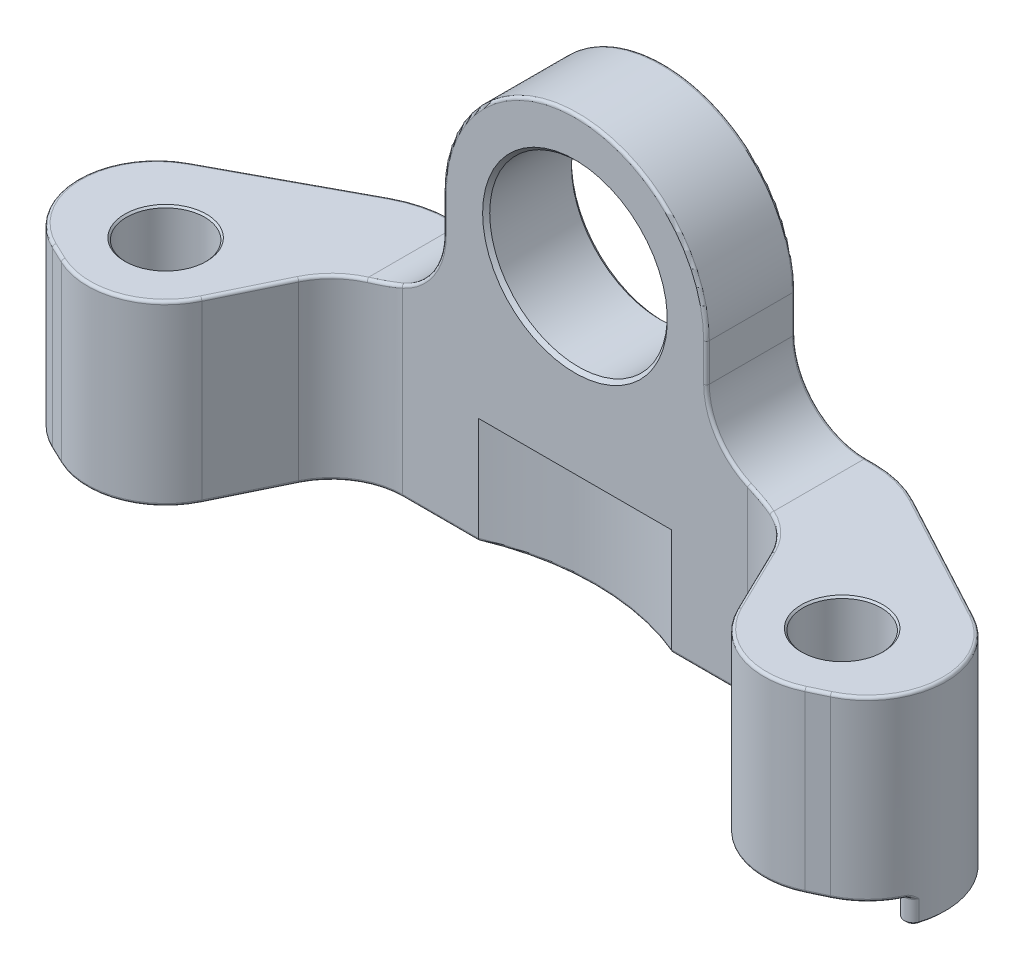
SolidWorks part; units mm, degrees
material "BOHLER M238"
ref_plane "Front Plane" through (0, 0, 0) normal (0, 0, 1) x (1, 0, 0)
ref_plane "Top Plane" through (0, 0, 0) normal (0, 1, 0) x (1, 0, 0)
ref_plane "Right Plane" through (0, 0, 0) normal (1, 0, 0) x (0, 0, -1)
sketch "Sketch1" plane through (0, 0, 0) normal (0, 1, 0) x (1, 0, 0)
  line L0 (0, 0) -> (0, 67.8527) construction
  line L1 (-59.4524, 45) -> (59.4524, 45)
  line L2 (0, 0) -> (0, -68.0986) construction
  line L3 (0, -44.3749) -> (-95.1623, 0) construction
  line L4 (0, -44.3749) -> (95.1623, 0) construction
  line L5 (73.649, 41.4283) -> (110.4109, 21.6808)
  line L6 (-73.649, 41.4283) -> (-110.4109, 21.6808)
  line L7 (109.4463, -17.5688) -> (104.6086, -19.8688)
  line L8 (66.4687, 8.7333) -> (75.3706, -9.6066)
  line L9 (48.4762, 20) -> (-48.4762, 20)
  line L10 (-66.4687, 8.7333) -> (-75.3706, -9.6066)
  line L11 (-109.4463, -17.5688) -> (-104.6086, -19.8688)
  arc A0 (109.4463, -17.5688) -> (110.4109, 21.6808) centre (100, 2.3) ccw
  arc A1 (-73.649, 41.4283) -> (-59.4524, 45) centre (-59.4524, 15) cw
  arc A2 (59.4524, 45) -> (73.649, 41.4283) centre (59.4524, 15) cw
  arc A3 (48.4762, 20) -> (66.4687, 8.7333) centre (48.4762, 0) cw
  arc A4 (-66.4687, 8.7333) -> (-48.4762, 20) centre (-48.4762, 0) cw
  arc A5 (-109.4463, -17.5688) -> (-110.4109, 21.6808) centre (-100, 2.3) cw
  circle A6 centre (-95.1623, 0) radius 11
  circle A7 centre (95.1623, 0) radius 11
  arc A8 (104.6086, -19.8688) -> (75.3706, -9.6066) centre (95.1623, 0) cw
  arc A9 (-75.3706, -9.6066) -> (-104.6086, -19.8688) centre (-95.1623, 0) cw
  circle A10 centre (0, -44.3749) radius 105 construction
  point P12 (0, 20)
  point P19 (0, 45)
  point P20 (-67, 45)
  point P23 (67, 45)
  point P26 (61, 20)
  point P29 (-61, 20)
  point P36 (84.8998, -29.239)
  point P39 (-84.8998, -29.239)
  dimension "D1" = 22
  dimension "D2" = 244
  dimension "D3" = 25
  dimension "D4" = 122
  dimension "D5" = 134
  dimension "D6" = 30
  dimension "D7" = 20
  dimension "D8" = 130
  dimension "D9" = 22
  dimension "D11" = 22
  dimension "D13" = 210
  dimension "D12" = 2.3
  dimension "D14" = 190.3246
  dimension "D10" = 20
extrude "Extrude1" add sketch "Sketch1" along normal blind 50
sketch "Sketch20" plane through (0, 0, -45) normal (0, 0, -1) x (-1, 0, 0)
  line L0 (-37, 80.6) -> (-37, 70)
  line L1 (37, 80.6) -> (37, 70)
  line L2 (-59.4524, 50) -> (59.4524, 50) construction
  line L3 (0, 80.6) -> (0, 15.3196) construction
  line L5 (57, 50) -> (0.0812, 50)
  line L6 (73.649, 50) -> (59.4524, 50) construction
  line L7 (-57, 50) -> (0.0812, 50)
  line L9 (-110.4109, 50) -> (-73.649, 50) construction
  line L10 (-110.4109, 0) -> (-73.649, 0) construction
  arc A0 (37, 80.6) -> (-37, 80.6) centre (0, 80.6) ccw
  circle A1 centre (0, 80.6) radius 24.9875
  arc A2 (37, 70) -> (57, 50) centre (57, 70) ccw
  arc A3 (-57, 50) -> (-37, 70) centre (-57, 70) ccw
  point P22 (37, 50)
  point P25 (-37, 50)
  dimension "D1" = 74
  dimension "D2" = 49.975
  dimension "D3" = 80.6
  dimension "D4" = 20
extrude "Boss-Extrude1" add sketch "Sketch20" against normal blind 40
sketch "Sketch21" plane through (0, 0, 0) normal (0, -1, 0) x (1, 0, 0)
  line L0 (-48.4762, -20) -> (48.4762, -20) construction
  line L1 (-48.4762, -20) -> (48.4762, -20)
  line L2 (-57, -18.0927) -> (-57, -5)
  line L3 (-57, -5) -> (57, -5)
  line L4 (57, -5) -> (-57, -5) construction
  line L5 (57, -5) -> (57, -18.0927)
  arc A0 (-57, -18.0927) -> (-48.4762, -20) centre (-48.4762, 0) ccw construction
  arc A1 (48.4762, -20) -> (57, -18.0927) centre (48.4762, 0) ccw construction
  arc A2 (-57, -18.0927) -> (-48.4762, -20) centre (-48.4762, 0) ccw
  arc A3 (48.4762, -20) -> (57, -18.0927) centre (48.4762, 0) ccw
extrude "Cut-Extrude6" cut sketch "Sketch21" against normal through all
chamfer "Chamfer6" distance 1 angle 45 2 edges at (-24.9875, 80.6, -45) (-24.9875, 80.6, -20)
sketch "Sketch24" plane through (0, 0, 0) normal (0, -1, 0) x (1, 0, 0)
  circle A0 centre (95.1623, 0) radius 14.515
  circle A1 centre (-95.1623, 0) radius 14.515
  dimension "D1" = 29.03
extrude "Cut-Extrude8" cut sketch "Sketch24" against normal blind 12
sketch "Sketch22" plane through (0, 0, 0) normal (0, -1, 0) x (1, 0, 0)
  line L0 (0, 0) -> (0, -36.5166) construction
  line L1 (-48.4762, -20) -> (48.4762, -20) construction
  line L2 (-27.1983, -20) -> (27.1983, -20)
  arc A0 (-27.1983, -20) -> (27.1983, -20) centre (0, 44.5) ccw
  dimension "D1" = 5.5
  dimension "D2" = 70
extrude "Cut-Extrude7" cut sketch "Sketch22" against normal blind 30
sketch "Sketch23" plane through (0, 0, 0) normal (0, -1, 0) x (1, 0, 0)
  line L0 (116.3612, 4.5259) -> (105.2255, -19.3547)
  line L1 (0, 0) -> (0, -63.7632) construction
  line L2 (-116.3612, 4.5259) -> (-105.2255, -19.3547)
  line L3 (-73.649, -41.4283) -> (-110.4109, -21.6808) construction
  line L4 (-108.6743, -22.6136) -> (-110.4109, -21.6808)
  line L5 (110.4109, -21.6808) -> (73.649, -41.4283) construction
  line L6 (110.4109, -21.6808) -> (108.6743, -22.6136)
  line L7 (59.4524, -45) -> (-59.4524, -45) construction
  line L9 (48.4762, -20) -> (27.1983, -20)
  line L10 (-27.1983, -20) -> (-48.4762, -20)
  line L11 (-66.4687, -8.7333) -> (-75.3706, 9.6066)
  line L12 (-104.6086, 19.8688) -> (-109.4463, 17.5688)
  line L13 (-110.4109, -21.6808) -> (-73.649, -41.4283)
  line L14 (-59.4524, -45) -> (59.4524, -45)
  line L15 (73.649, -41.4283) -> (110.4109, -21.6808)
  line L16 (109.4463, 17.5688) -> (104.6086, 19.8688)
  line L17 (75.3706, 9.6066) -> (66.4687, -8.7333)
  circle A1 centre (-95.1623, 0) radius 14.515 construction
  circle A2 centre (-95.1623, 0) radius 14.515 construction
  arc A3 (121.0151, 4.209) -> (116.3612, 4.5259) centre (118.627, 3.4694) ccw
  arc A4 (-116.3612, 4.5259) -> (-121.0151, 4.209) centre (-118.627, 3.4694) ccw
  arc A5 (105.2255, -19.3547) -> (108.6743, -22.6136) centre (107.4913, -20.4112) ccw
  arc A6 (-105.2255, -19.3547) -> (-108.6743, -22.6136) centre (-107.4913, -20.4112) cw
  arc A9 (-27.1983, -20) -> (27.1983, -20) centre (0, 44.5) ccw
  arc A10 (-66.4687, -8.7333) -> (-48.4762, -20) centre (-48.4762, 0) ccw
  arc A11 (-75.3706, 9.6066) -> (-104.6086, 19.8688) centre (-95.1623, 0) ccw
  arc A12 (-109.4463, 17.5688) -> (-110.4109, -21.6808) centre (-100, -2.3) ccw
  arc A13 (-73.649, -41.4283) -> (-59.4524, -45) centre (-59.4524, -15) ccw
  arc A14 (59.4524, -45) -> (73.649, -41.4283) centre (59.4524, -15) ccw
  arc A15 (110.4109, -21.6808) -> (109.4463, 17.5688) centre (100, -2.3) ccw
  arc A16 (104.6086, 19.8688) -> (75.3706, 9.6066) centre (95.1623, 0) ccw
  arc A17 (48.4762, -20) -> (66.4687, -8.7333) centre (48.4762, 0) ccw
  arc A21 (-121.0151, 4.209) -> (-110.4109, -21.6808) centre (-100, -2.3) ccw
  arc A24 (110.4109, -21.6808) -> (121.0151, 4.209) centre (100, -2.3) ccw
  dimension "D2" = 17.3
  dimension "D4" = 2.5
  dimension "D5" = 2.5
  dimension "D3" = 65
  dimension "D1" = 0
extrude "Boss-Extrude2" add sketch "Sketch23" along normal blind 7
sketch "Sketch25" plane through (0, 0, -45) normal (0, 0, -1) x (-1, 0, 0)
  line L0 (-30.6766, 19.1685) -> (34.6606, 19.1685) construction
  text T0 "\r\n11111 - XX" font "Century Gothic" height 4
extrude "Cut-Extrude9" cut sketch "Sketch25" against normal blind 0.01
chamfer "Chamfer7" distance 0.5 angle 45 6 edges at (-95.1623, 0, -14.515) (-95.1623, 12, -11) (95.1623, 12, -11) (95.1623, 0, -14.515) (-95.1623, 50, 11) (95.1623, 50, -11)
fillet "Fillet1" radius 0.8 6 edges at (118.7968, 0, 5.9636) (105.7743, 0, -22.2283) (110.7934, 0, -7.4144) (-110.7934, 0, -7.4144)
fillet "Fillet2" radius 0.8 50 edges at (-107.0274, 50, 18.7188) (-121.9934, 50, -1.7595) (-92.0299, 50, -31.5545) (-66.7719, 50, -44.0934) (-58.2262, 50, -45) (-42.8579, 55.8579, -45) (-37, 75.3, -45) (0, 117.6, -45) (37, 75.3, -45) (42.8579, 55.8579, -45) (58.2262, 50, -45) (66.7719, 50, -44.0934) (92.0299, 50, -31.5545) (121.9934, 50, -1.7595) (107.0274, 50, 18.7188) (87.8764, 50, 20.7585) (70.9196, 50, 0.4367) (62.536, 50, -14.224) (52.3031, 50.5593, -19.6305) (40.111, 59.2873, -20) (37, 75.3, -20) (0, 117.6, -20) (-37, 75.3, -20) (-40.111, 59.2873, -20) (-53.1731, 50.3695, -19.4407) (-62.536, 50, -14.224) (-70.9196, 50, 0.4367) (-87.8764, 50, 20.7585) (-120.5268, -0.1279, 5.6152) (-107.0274, 0, 18.7188) (-37.8373, 0, -20) (-59.0907, 0, -16.9509) (-70.9196, 0, 0.4367) (-87.8764, 0, 20.7585) (120.5268, -0.1279, 5.6152) (115.8597, 0, 12.9469) (107.0274, 0, 18.7188) (87.8764, 0, 20.7585) (70.9196, 0, 0.4367) (59.0907, 0, -16.9509) (107.4158, -0.1195, -23.2896) (90.2129, 0, -32.5306) (66.7719, 0, -44.0934) (0, 0, -45) (-66.7719, 0, -44.0934) (-107.4158, -0.1195, -23.2896) (0, 0, -25.5) (37.8373, 0, -20)
chamfer "Chamfer8" distance 0.5 angle 45 10 edges at (120.3585, -7, -10.6386) (109.5426, -7, -22.1472) (118.7968, -7, 5.9636) (105.7743, -7, -22.2283) (110.7934, -7, -7.4144) (-110.7934, -7, -7.4144) (-105.7743, -7, -22.2283) (-118.7968, -7, 5.9636) (-109.5426, -7, -22.1472) (-120.3585, -7, -10.6386)
